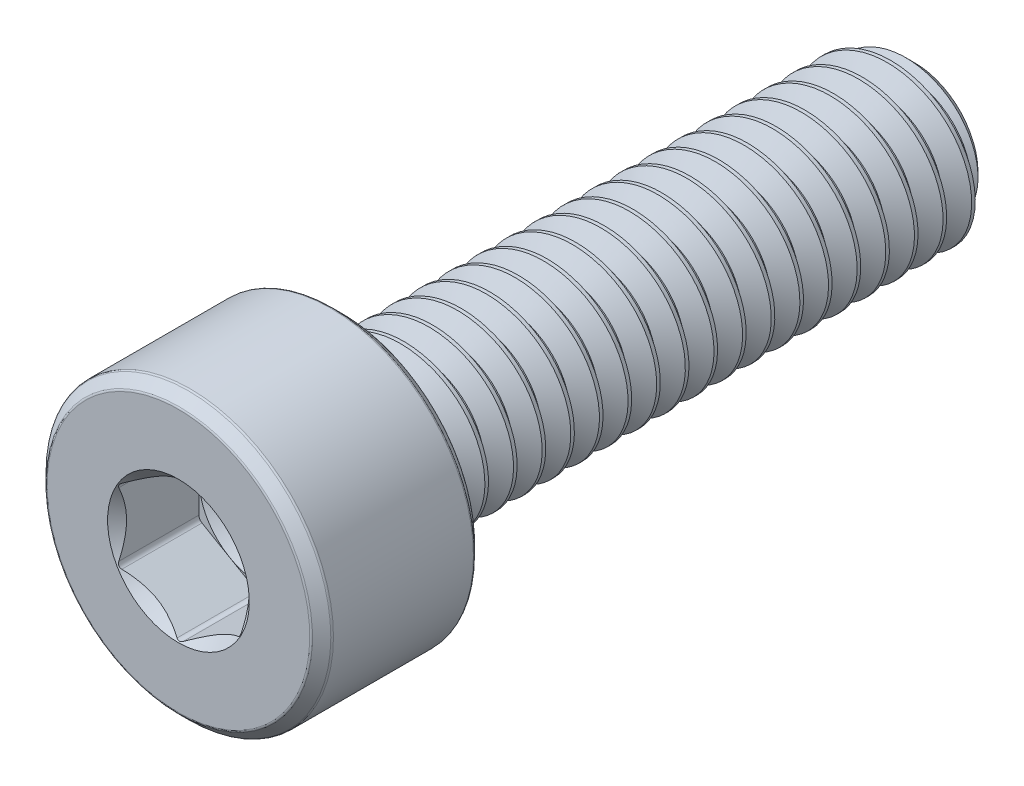
SolidWorks part; units mm, degrees
material "AISI 316 Stainless Steel Sheet (SS)"
ref_plane "Front Plane" through (0, 0, 0) normal (0, 0, 1) x (1, 0, 0)
ref_plane "Top Plane" through (0, 0, 0) normal (0, 1, 0) x (1, 0, 0)
ref_plane "Right Plane" through (0, 0, 0) normal (1, 0, 0) x (0, 0, -1)
sketch "Sketch1" plane through (0, 0, 0) normal (1, 0, 0) x (0, 0, -1)
  line L0 (-9, 0) -> (9, 0) construction
  line L1 (-9, 0) -> (-9, 3.5)
  line L2 (-9, 3.5) -> (-5, 3.5)
  line L3 (-5, 3.5) -> (-5, 2)
  line L4 (-5, 2) -> (8.5453, 2)
  line L5 (8.9562, 2.0758) -> (9.3062, 1.4696) construction
  line L6 (9.3062, 1.4696) -> (9.6562, 2.0758) construction
  line L7 (9.6562, 2.0758) -> (8.9562, 2.0758) construction
  line L8 (8.5453, 2) -> (9, 1.5453)
  line L9 (9, 1.5453) -> (9, 0)
  line L10 (9, 2) -> (9.6125, 2) construction
  line L11 (9.3062, 2.0758) -> (9.3062, 2) construction
  line L12 (9.3062, 2) -> (9.3062, 1.5453) construction
  line L13 (9.3062, 1.5453) -> (9.3062, 1.4696) construction
  line L14 (9.2625, 1.5453) -> (9.35, 1.5453)
  line L15 (8.9781, 2.0379) -> (9.6344, 2.0379)
  line L16 (9.35, 1.5453) -> (9.6344, 2.0379)
  line L17 (9.2625, 1.5453) -> (8.9781, 2.0379)
  line L18 (-9, 1.5) -> (-7, 1.5)
  line L19 (-7, 1.5) -> (-7, 0)
  line L20 (6.55, 2) -> (6.55, -2) construction
  point P20 (9.3062, 2.0379)
  point P22 (6.55, -2)
  point P28 (6.55, 0)
  point P29 (8.5453, -2)
  dimension "Head Diameter" = 7
  dimension "Length" = 14
  dimension "Head Height" = 4
  dimension "Thread Size" = 4
  dimension "D1" = 45
  dimension "Thread Pitch" = 0.7
  dimension "D3" = 0.0875
  dimension "Drive Size" = 3
  dimension "D4" = 2.45
  dimension "D5" = 2
sketch "Sketch3" plane through (0, 0, 0) normal (1, 0, 0) x (0, 0, -1)
  line L0 (-9, 3.2103) -> (-9, 1.5)
  line L1 (-9, 1.5) -> (-7, 1.5)
  line L2 (-7, 1.5) -> (-7, 0)
  line L3 (-7, 0) -> (9, 0)
  line L4 (9, 0) -> (9, 1.5453)
  line L5 (9, 1.5453) -> (8.5453, 2)
  line L6 (8.5453, 2) -> (-5, 2)
  line L7 (-5, 2) -> (-5, 3.2103)
  line L8 (-5.2897, 3.5) -> (-8.7103, 3.5)
  line L9 (-8.9808, 3.2567) -> (-8.7567, 3.4808)
  line L11 (-9, 3.5) -> (-5, 3.5) construction
  line L12 (-5.2433, 3.4808) -> (-5.0192, 3.2567)
  arc A5 (-5.0192, 3.2567) -> (-5, 3.2103) centre (-5.0656, 3.2103) cw
  arc A6 (-5.2897, 3.5) -> (-5.2433, 3.4808) centre (-5.2897, 3.4344) cw
  arc A7 (-8.7103, 3.5) -> (-8.7567, 3.4808) centre (-8.7103, 3.4344) ccw
  arc A8 (-9, 3.2103) -> (-8.9808, 3.2567) centre (-8.9344, 3.2103) cw
  point P17 (-7, 3.5)
  point P29 (-9, 3.2375)
  dimension "D3" = 0.0656
  dimension "D1" = 45
  dimension "D2" = 0.2625
revolve "Revolve1" add sketch "Sketch3" angle 360 about L0
sketch "Sketch4" plane through (0, 0, 9) normal (0, 0, 1) x (1, 0, 0)
  line L1 (0, 1.7321) -> (-1.5, 0.866)
  line L2 (-1.5, 0.866) -> (-1.5, -0.866)
  line L3 (-1.5, -0.866) -> (0, -1.7321)
  line L4 (0, -1.7321) -> (1.5, -0.866)
  line L5 (1.5, -0.866) -> (1.5, 0.866)
  line L6 (1.5, 0.866) -> (0, 1.7321)
  circle A0 centre (0, 0) radius 1.5 construction
extrude "Cut-Extrude1" cut sketch "Sketch4" against normal up to vertex (2 mm away) up to point (0, 1.5, 7)
sketch "Sketch5" plane through (0, 0, 9) normal (0, 0, 1) x (1, 0, 0)
  circle A0 centre (0, 0) radius 1.7321
extrude "Cut-Extrude2" cut sketch "Sketch5" against normal up to next (2 mm away) draft 45
sketch "Sketch10" plane through (0, 0, 7) normal (0, 0, 1) x (1, 0, 0)
  line L0 (1.5, 0.866) -> (1.5, -0.866) construction
  circle A0 centre (0, 0) radius 1.5
extrude "Cut-Extrude3" cut sketch "Sketch10" against normal through all draft 60
fillet "Fillet1" radius 0.15 6 edges at (-1.5, 0.866, 8) (0, 1.7321, 8) (1.5, 0.866, 8) (1.5, -0.866, 8) (0, -1.7321, 8) (-1.5, -0.866, 8)
sketch "Sketch6" plane through (0, 0, -9) normal (0, 0, -1) x (-1, 0, 0)
  circle A0 centre (0, 0) radius 2 construction
  circle A1 centre (0, 0) radius 2
curve "Helix/Spiral1" pitch 0.7 height 14.7 radius 2 centre (0, 0, -9) axis (0, 0, 1) start towards (0, 1, 0)
sketch "Sketch7" plane through (0, 0, 0) normal (1, 0, 0) x (0, 0, -1)
  line L0 (9.2625, 1.5453) -> (9.35, 1.5453) construction
  line L1 (9.2625, 1.5453) -> (8.9781, 2.0379) construction
  line L2 (8.9781, 2.0379) -> (9.6344, 2.0379) construction
  line L3 (9.35, 1.5453) -> (9.6344, 2.0379) construction
  line L4 (9.2625, 1.5453) -> (9.35, 1.5453)
  line L5 (9.2625, 1.5453) -> (8.9781, 2.0379)
  line L6 (8.9781, 2.0379) -> (9.6344, 2.0379)
  line L7 (9.35, 1.5453) -> (9.6344, 2.0379)
sweep "Cut-Sweep1" cut profiles "Sketch7" path "Helix/Spiral1" align with end faces yes
sketch "Sketch11" plane through (0, 0, 0) normal (1, 0, 0) x (0, 0, -1)
  line L0 (-5, 2.175) -> (-4.825, 2) construction
  line L1 (-5, 3.5) -> (-5, 2) construction
  line L2 (-5, 2) -> (8.5453, 2) construction
  line L3 (-4.825, 2) -> (-4.65, 2)
  line L4 (-4.65, 2) -> (-2.65, 0)
  line L5 (-9, 0) -> (9, 0) construction
  line L6 (-2.65, 0) -> (-5, 0)
  line L7 (-5, 0) -> (-5, 2.175) construction
  line L8 (-5, 2.175) -> (-6.134, 2.175)
  line L9 (-6.134, 2.175) -> (-6.134, 0)
  line L10 (-6.134, 0) -> (-5, 0)
  arc A0 (-4.825, 2) -> (-5, 2.175) centre (-4.825, 2.175) cw
  dimension "D1" = 45
  dimension "D2" = 0.175
  dimension "D3" = 45
  dimension "D4" = 0.35
revolve "Revolve2" add sketch "Sketch11" angle 360 about L6
equation "\"D3@Sketch1\" = \"Thread Pitch@Sketch1\" / 8"
equation "\"D4@Sketch1\" = \"Thread Pitch@Sketch1\" * 3.5"
equation "\"D3@Helix/Spiral1\" = \"Length@Sketch1\" + \"Thread Pitch@Sketch1\""
equation "\"D4@Helix/Spiral1\" = \"Thread Pitch@Sketch1\""
equation "\"D5@Sketch1\"=\"Head Height@Sketch1\"*0.5"
equation "\"D2@Sketch3\"=\"Head Diameter@Sketch1\" *0.0375"
equation "\"D2@Sketch11\"=\"Thread Pitch@Sketch1\" / 4"
equation "\"D4@Sketch11\"=\"Thread Pitch@Sketch1\"/2"
equation "\"D1@Fillet1\"=\"Drive Size@Sketch1\"*0.05"
equation "\"D1@Fillet1\" = \"Drive Size@Sketch1\" * 0.05"
equation "\"D3@Sketch3\"=\"D2@Sketch3\"*0.25"
